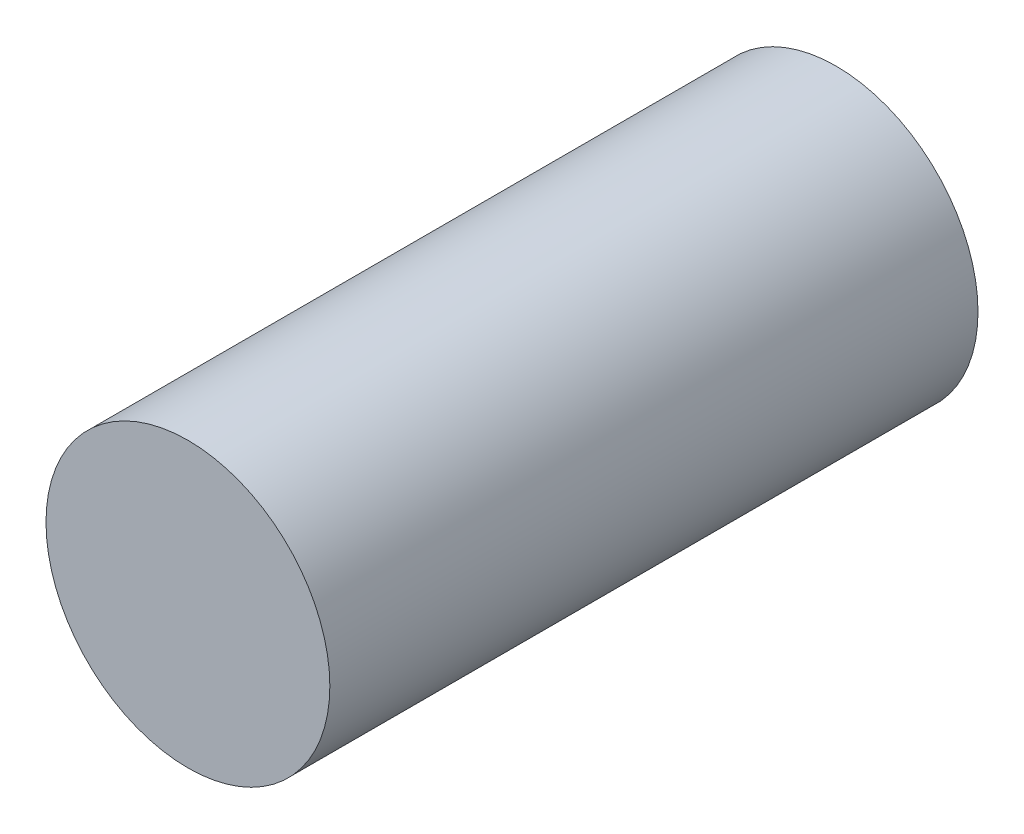
SolidWorks part; units mm, degrees
ref_plane "Front Plane" through (0, 0, 0) normal (0, 0, 1) x (1, 0, 0)
ref_plane "Top Plane" through (0, 0, 0) normal (0, 1, 0) x (1, 0, 0)
ref_plane "Right Plane" through (0, 0, 0) normal (1, 0, 0) x (0, 0, -1)
sketch "Sketch1" plane through (0, 0, 0) normal (0, 0, 1) x (1, 0, 0)
  circle A0 centre (0, 0) radius 6.35
  dimension "D1" = 12.7
extrude "Boss-Extrude1" add sketch "Sketch1" along normal blind 29
